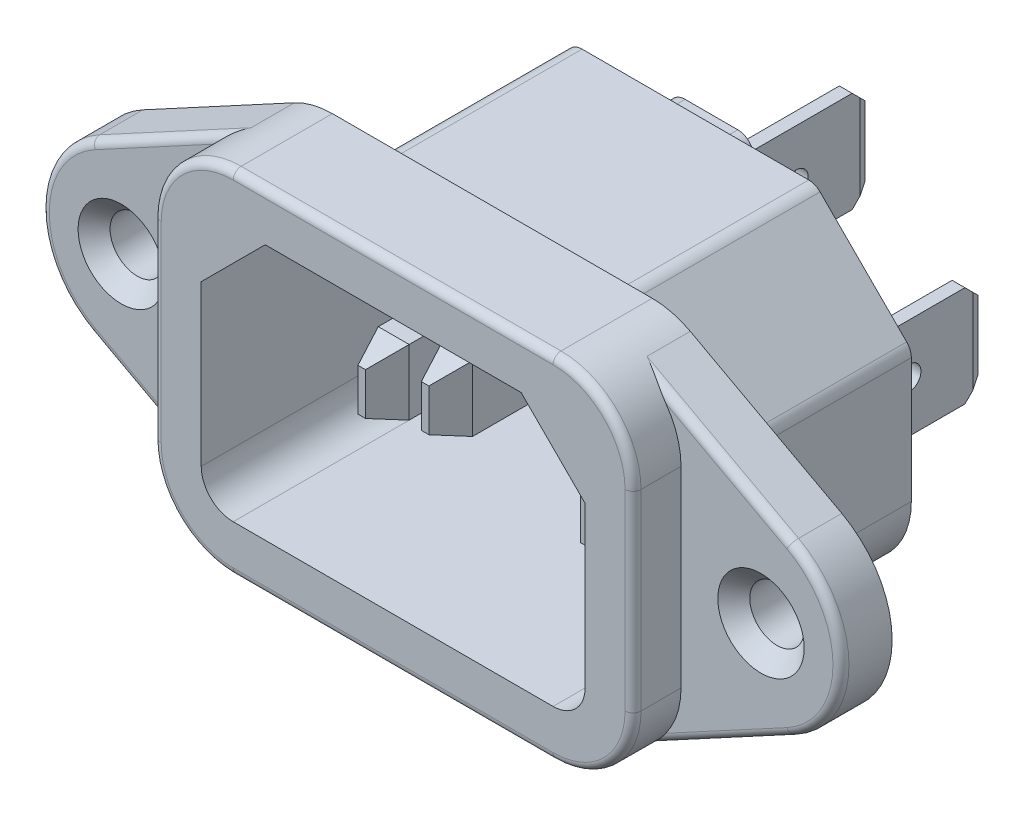
SolidWorks part; units mm, degrees
ref_plane "Front Plane" through (0, 0, 0) normal (0, 0, 1) x (1, 0, 0)
ref_plane "Top Plane" through (0, 0, 0) normal (0, 1, 0) x (1, 0, 0)
ref_plane "Right Plane" through (0, 0, 0) normal (1, 0, 0) x (0, 0, -1)
sketch "Sketch1" plane through (0, 0, 0) normal (0, 0, 1) x (1, 0, 0)
  line L0 (0, 11) -> (-10, 11)
  line L1 (-12.377, 10.3988) -> (-21.8524, 5.2786)
  line L2 (-21.8524, -5.2786) -> (-12.377, -10.3988)
  line L3 (-10, -11) -> (0, -11)
  line L4 (0, 11) -> (0, -11)
  line L5 (0, 0) -> (-19, 0) construction
  line L6 (-10, -11) -> (-10, 11) construction
  line L7 (-12.377, 10.3988) -> (-12.377, -10.3988) construction
  arc A0 (-10, 11) -> (-12.377, 10.3988) centre (-10, 6) ccw
  arc A1 (-10, -11) -> (-12.377, -10.3988) centre (-10, -6) cw
  arc A2 (-21.8524, 5.2786) -> (-21.8524, -5.2786) centre (-19, 0) ccw
  circle A3 centre (-20, 0) radius 1.7
  point P2 (0, 0)
  point P16 (-25, 0)
  dimension "D2" = 5
  dimension "D3" = 6
  dimension "D4" = 3.4
  dimension "D5" = 20
  dimension "D6" = 25
  dimension "D1" = 22
  dimension "D7" = 10
extrude "flange" add sketch "Sketch1" along normal blind 3.2
sketch "Sketch2" plane through (0, 0, 3.2) normal (0, 0, 1) x (1, 0, 0)
  line L1 (0, 11) -> (-10, 11)
  line L2 (0, 11) -> (-10, 11) construction
  line L3 (0, -11) -> (0, 11) construction
  line L4 (-15, 6) -> (-15, -6)
  line L5 (-10, -11) -> (0, -11)
  line L6 (-10, -11) -> (0, -11) construction
  arc A0 (-10, 11) -> (-15, 6) centre (-10, 6) ccw
  arc A2 (-10, -11) -> (-15, -6) centre (-10, -6) cw
  line M1 (0, -11) -> (0, 11)
  line M2 (0, 11) -> (-10, 11)
  line M8 (-10, -11) -> (0, -11)
  dimension "D1" = 5
  dimension "D2" = 15
extrude "top" add sketch "Sketch2" along normal blind 3 contours A2 A0 L4 M8 M1 M2 region at (-7.2855, 0, 3.2)
sketch "Sketch4" plane through (0, 0, 0) normal (0, 0, -1) x (-1, 0, 0)
  line L0 (0, -9.6) -> (8.5, -9.6)
  line L1 (0, -11) -> (0, 11) construction
  line L2 (13.5, -4.6) -> (13.5, 3.1858)
  line L3 (7.0858, 9.6) -> (0, 9.6)
  line L4 (13.2071, 3.8929) -> (7.7929, 9.3071)
  line L5 (0, -9.6) -> (0, 9.6)
  arc A0 (8.5, -9.6) -> (13.5, -4.6) centre (8.5, -4.6) ccw
  arc A1 (7.7929, 9.3071) -> (7.0858, 9.6) centre (7.0858, 8.6) ccw
  arc A2 (13.5, 3.1858) -> (13.2071, 3.8929) centre (12.5, 3.1858) ccw
  point P4 (13.5, 9.6)
  point P10 (0, 0)
  point P14 (7.5, 9.6)
  point P17 (13.5, 3.6)
  dimension "D3" = 5
  dimension "D4" = 1
  dimension "D1" = 19.2
  dimension "D2" = 13.5
extrude "rear" add sketch "Sketch4" along normal blind 12.7
sketch "Sketch3" plane through (0, 0, 6.2) normal (0, 0, 1) x (1, 0, 0)
  line L0 (0, -8) -> (-10, -8)
  line L1 (0, -11) -> (0, 11) construction
  line L2 (-12, -6) -> (-12, 4)
  line L3 (-12, 4) -> (-8, 8)
  line L4 (-8, 8) -> (0, 8)
  line L5 (0, 8) -> (0, -8)
  line L6 (0, 8) -> (0, -8)
  arc A0 (-10, -8) -> (-12, -6) centre (-10, -6) cw
  point P9 (0, 0)
  line M3 (0, -11) -> (0, 11)
  dimension "D3" = 2
  dimension "D1" = 12
  dimension "D2" = 16
  dimension "D4" = 12
  dimension "D5" = 135
extrude "socket" cut sketch "Sketch3" against normal blind 17 contours A0 L0 L4 L3 L2 M3 region at (-5.7701, -0.2558, 6.2)
chamfer "Chamfer2" distance 1 angle 45 1 edges at (-18.3, 0, 3.2)
mirror "Mirror1" about plane through (0, 0, 0) normal (1, 0, 0) of bodies 105
sketch "Sketch5" plane through (0, 0, -10.8) normal (0, 0, 1) x (1, 0, 0)
  line L0 (-6, -1.95) -> (6, -1.95) construction
  line L1 (-7.93, 0.1) -> (-6, 0.1)
  line L2 (-7.93, 0.1) -> (-7.93, -4)
  line L3 (-7.93, -4) -> (-6, -4)
  line L4 (-6, 0.1) -> (-6, -4)
  line L5 (0, 8) -> (0, -8) construction
  line L6 (7.93, 0.1) -> (6, 0.1)
  line L7 (7.93, 0.1) -> (7.93, -4)
  line L8 (7.93, -4) -> (6, -4)
  line L9 (6, 0.1) -> (6, -4)
  line L10 (-0.965, 4.2) -> (0.965, 4.2)
  line L11 (-0.965, 4.2) -> (-0.965, 0.1)
  line L12 (-0.965, 0.1) -> (0.965, 0.1)
  line L13 (0.965, 4.2) -> (0.965, 0.1)
  line L14 (-8, 8) -> (8, 8) construction
  line L15 (10, -8) -> (-10, -8) construction
  point P20 (0, -1.95)
  point P21 (0, 0.1)
  dimension "D1" = 1.93
  dimension "D2" = 4.1
  dimension "D3" = 12
  dimension "D4" = 6.05
extrude "pin" add sketch "Sketch5" along normal blind 12
sketch "Sketch6" plane through (0, 0, 1.2) normal (0, 0, 1) x (1, 0, 0)
  line L4 (-0.965, 4.2) -> (-0.965, 0.1)
  line L5 (-0.965, 0.1) -> (0.965, 0.1)
  line L6 (0.965, 0.1) -> (0.965, 4.2)
  line L7 (0.965, 4.2) -> (-0.965, 4.2)
  line L8 (-0.965, 4.2) -> (-0.965, 0.1)
  line L9 (-0.965, 0.1) -> (0.965, 0.1)
  line L10 (0.965, 0.1) -> (0.965, 4.2)
  line L11 (0.965, 4.2) -> (-0.965, 4.2)
  dimension "D1" = 0
extrude "pinGnd" add sketch "Sketch6" along normal blind 3
chamfer "Chamfer1" distance 2 angle 20 12 edges at (6.965, 0.1, 1.2) (7.93, -1.95, 1.2) (6.965, -4, 1.2) (6, -1.95, 1.2) (-6.965, 0.1, 1.2) (-7.93, -1.95, 1.2) (-6.965, -4, 1.2) (-6, -1.95, 1.2) (0, 4.2, 4.2) (0.965, 2.15, 4.2) (0, 0.1, 4.2) (-0.965, 2.15, 4.2) first distance on face at (6.965, 0.1, -4.8) first distance on face at (7.93, -1.95, -4.8) first distance on face at (6.965, -4, -4.8) first distance on face at (6, -1.95, -4.8) first distance on face at (-6.965, 0.1, -4.8) first distance on face at (-7.93, -1.95, -4.8) first distance on face at (-6.965, -4, -4.8) first distance on face at (-6, -1.95, -4.8) first distance on face at (0, 4.2, -3.3) first distance on face at (0.965, 2.15, -3.3) first distance on face at (0, 0.1, -3.3) first distance on face at (-0.965, 2.15, -3.3)
sketch "Sketch8" plane through (0, 0, -12.7) normal (0, 0, -1) x (-1, 0, 0)
  line L0 (-8.5, -9.6) -> (8.5, -9.6) construction
  line L1 (-8.7, 2.1) -> (-5.4, 2.1)
  line L2 (-9.7, 1.1) -> (-9.7, -8.1)
  line L3 (-8.7, -9.1) -> (-5.4, -9.1)
  line L4 (-4.4, 1.1) -> (-4.4, -8.1)
  arc A0 (-8.7, 2.1) -> (-9.7, 1.1) centre (-8.7, 1.1) ccw
  arc A1 (-4.4, 1.1) -> (-5.4, 2.1) centre (-5.4, 1.1) ccw
  arc A2 (-5.4, -9.1) -> (-4.4, -8.1) centre (-5.4, -8.1) ccw
  arc A3 (-9.7, -8.1) -> (-8.7, -9.1) centre (-8.7, -8.1) ccw
  point P14 (0, -9.6)
  dimension "D1" = 1
  dimension "D2" = 5.3
  dimension "D3" = 11.2
  dimension "D4" = 0.5
  dimension "D5" = 4.4
extrude "Extrude8" add sketch "Sketch8" along normal blind 1
sketch "Sketch9" plane through (0, 0, -12.7) normal (0, 0, -1) x (-1, 0, 0)
  line L0 (-4.4, -8.1) -> (-4.4, 1.1) construction
  line L2 (7.0858, 9.6) -> (-7.0858, 9.6) construction
  point P0 (0, 3.5)
  point P1 (7.05, -3.5)
  point P5 (-4.4, -3.5)
  dimension "D1" = 11.45
  dimension "D2" = 0
  dimension "D3" = 6.1
pattern_sketch "Sketch-Pattern1" of "Extrude8" driven by "Sketch9"
sketch "Sketch10" plane through (0, 0, -13.7) normal (0, 0, -1) x (-1, 0, 0)
  line L0 (7.05, 2.1) -> (7.05, -9.1) construction
  line L1 (0, 6.65) -> (-0.8, 6.65)
  line L2 (0, 6.65) -> (0, 0.35)
  line L3 (0, 0.35) -> (-0.8, 0.35)
  line L4 (-0.8, 6.65) -> (-0.8, 0.35)
  line L5 (7.05, -0.35) -> (6.25, -0.35)
  line L6 (7.05, -0.35) -> (7.05, -6.65)
  line L7 (7.05, -6.65) -> (6.25, -6.65)
  line L8 (6.25, -0.35) -> (6.25, -6.65)
  line L9 (-7.05, -0.35) -> (-7.85, -0.35)
  line L10 (-7.05, -0.35) -> (-7.05, -6.65)
  line L11 (-7.05, -6.65) -> (-7.85, -6.65)
  line L12 (-7.85, -0.35) -> (-7.85, -6.65)
  line L14 (8.7, 2.1) -> (5.4, 2.1) construction
  line L15 (5.4, -9.1) -> (8.7, -9.1) construction
  line L16 (-7.05, 2.1) -> (-7.05, -9.1) construction
  line L17 (-5.4, 2.1) -> (-8.7, 2.1) construction
  line L18 (-8.7, -9.1) -> (-5.4, -9.1) construction
  line L19 (0, 9.1) -> (0, -2.1) construction
  line L20 (1.65, 9.1) -> (-1.65, 9.1) construction
  line L21 (-1.65, -2.1) -> (1.65, -2.1) construction
  point P18 (7.05, -3.5)
  point P25 (-7.05, -3.5)
  point P32 (0, 3.5)
  dimension "D1" = 0.8
  dimension "D2" = 6.3
extrude "rear_blades" add sketch "Sketch10" along normal blind 9
chamfer "blade_chmf" distance 1 angle 45 6 edges at (-6.65, -0.35, -22.7) (-6.65, -6.65, -22.7) (0.4, 6.65, -22.7) (0.4, 0.35, -22.7) (7.45, -0.35, -22.7) (7.45, -6.65, -22.7)
chamfer "blade_chmf2" distance 0.5 angle 20 6 edges at (-7.05, -3.5, -22.7) (-6.25, -3.5, -22.7) (7.85, -3.5, -22.7) (7.05, -3.5, -22.7) (0.8, 3.5, -22.7) (0, 3.5, -22.7) first distance on face at (-7.05, -3.5, -19.3667) first distance on face at (-6.25, -3.5, -19.3667) first distance on face at (7.85, -3.5, -19.3667) first distance on face at (7.05, -3.5, -19.3667) first distance on face at (0.8, 3.5, -19.3667) first distance on face at (0, 3.5, -19.3667)
fillet "Fillet1" radius 0.5 11 edges at (25, 0, 3.2) (-25, 0, 3.2) (13.5355, -9.5355, 6.2) (0, -11, 6.2) (-13.5355, -9.5355, 6.2) (-15, 0, 6.2) (-13.5355, 9.5355, 6.2)
sketch "Sketch11" plane through (-7.05, 0, 0) normal (-1, 0, 0) x (0, 0, 1)
  line L0 (-22.2, -3.5) -> (-18.95, -3.5) construction
  line L1 (-22.2, -0.85) -> (-22.2, -6.15) construction
  line L2 (-18.2, -3.5) -> (-18.2, 3.5) construction
  line L3 (-22.2, 6.15) -> (-22.2, 0.85) construction
  line L4 (-22.2, 6.15) -> (-22.2, 0.85)
  line L5 (-22.2, 3.5) -> (-18.2, 3.5) construction
  circle A0 centre (-18.2, -3.5) radius 0.75
  circle A1 centre (-18.2, 3.5) radius 0.75
  point P6 (-18.95, -3.5)
  dimension "D1" = 1.5
  dimension "D2" = 3.25
extrude "Extrude9" cut sketch "Sketch11" against normal through all contours A0 | A1 region at (-7.05, -3.5, -18.2) region at (-7.05, 3.5, -18.2)
